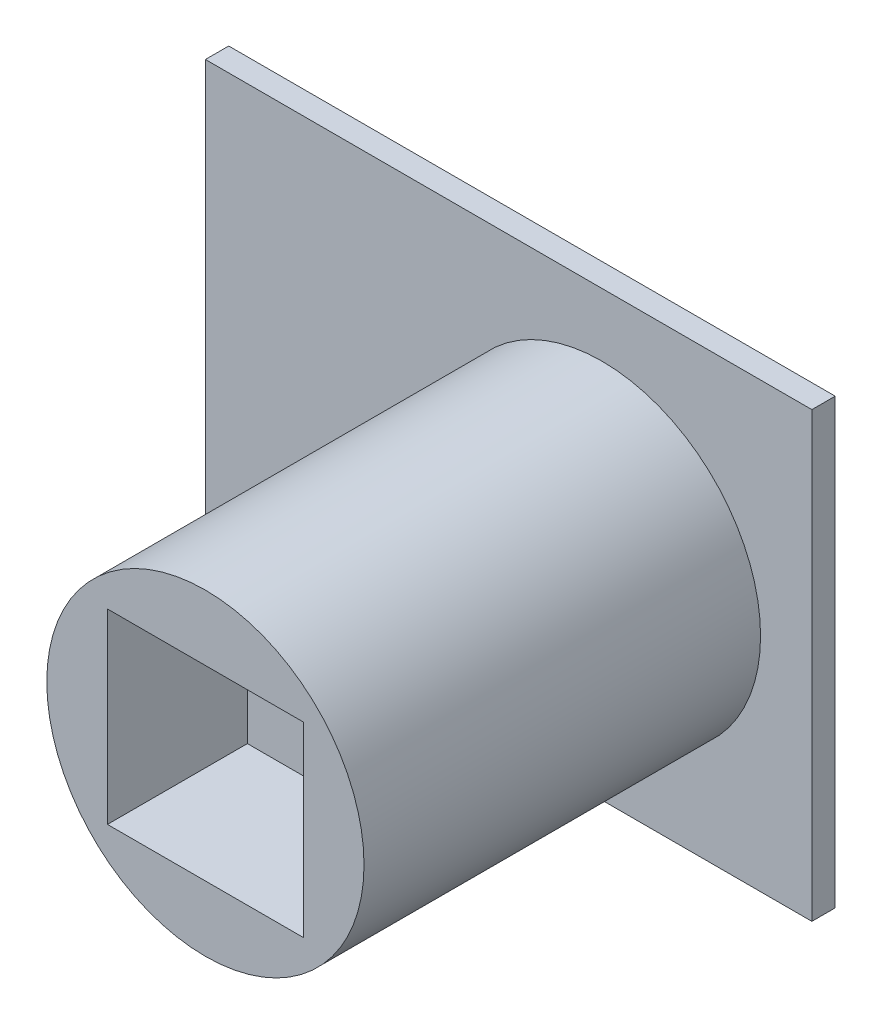
SolidWorks part; units mm, degrees
ref_plane "Alzado" through (0, 0, 0) normal (0, 0, 1) x (1, 0, 0)
ref_plane "Planta" through (0, 0, 0) normal (0, 1, 0) x (1, 0, 0)
ref_plane "Vista lateral" through (0, 0, 0) normal (1, 0, 0) x (0, 0, -1)
sketch "Croquis1" plane through (0, 0, 0) normal (0, 0, 1) x (1, 0, 0)
  line L1 (-65, -47.5) -> (65, -47.5)
  line L2 (-65, -47.5) -> (-65, 47.5)
  line L3 (-65, 47.5) -> (65, 47.5)
  line L4 (65, -47.5) -> (65, 47.5)
  line L5 (-65, -47.5) -> (65, 47.5) construction
  line L6 (-65, 47.5) -> (65, -47.5) construction
  point P0 (0, 0)
  dimension "D1" = 130
  dimension "D2" = 95
extrude "Saliente-Extruir1" add sketch "Croquis1" along normal blind 5
sketch "Croquis2" plane through (0, 0, 5) normal (0, 0, 1) x (1, 0, 0)
  line L0 (0, 0) -> (20, 0) construction
  circle A0 centre (20, 0) radius 34
  dimension "D2" = 68
  dimension "D1" = 20
extrude "Saliente-Extruir2" add sketch "Croquis2" along normal blind 85
sketch "Croquis3" plane through (0, 0, 90) normal (0, 0, 1) x (1, 0, 0)
  line L1 (-1, -20) -> (41, -20)
  line L2 (-1, -20) -> (-1, 20)
  line L3 (-1, 20) -> (41, 20)
  line L4 (41, -20) -> (41, 20)
  line L5 (-1, -20) -> (41, 20) construction
  line L6 (-1, 20) -> (41, -20) construction
  point P0 (20, 0)
  dimension "D1" = 42
  dimension "D2" = 40
extrude "Cortar-Extruir1" cut sketch "Croquis3" against normal blind 30
